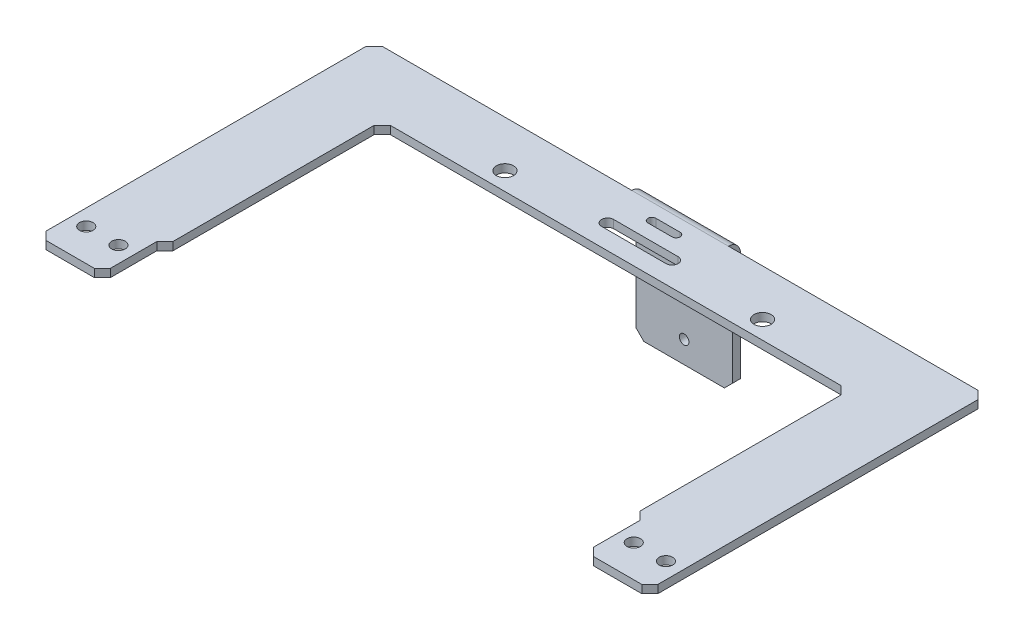
SolidWorks part; units mm, degrees
note: The reader was unsure of these and kept them because the rebuilt part matched: flange length of "Edge-Flange1".
material "5052-H32"
ref_plane "Front" through (0, 0, 0) normal (0, 0, 1) x (1, 0, 0)
ref_plane "Top" through (0, 0, 0) normal (0, 1, 0) x (1, 0, 0)
ref_plane "Right" through (0, 0, 0) normal (1, 0, 0) x (0, 0, -1)
sketch "Sketch1" plane through (0, 0, 0) normal (0, 1, 0) x (1, 0, 0)
  line L0 (0, 0) -> (331.8997, 0) construction
  line L1 (0, 12.7) -> (337.5621, 12.7) construction
  line L2 (0, 24.638) -> (331.8997, 24.638) construction
  line L7 (25.4, 0) -> (0, 0)
  line L8 (0, 0) -> (0, 132.588)
  line L11 (25.4, 0) -> (25.4, 21.463)
  line L12 (25.4, 21.463) -> (28.575, 24.638)
  line L13 (28.575, 24.638) -> (28.575, 107.188)
  line L14 (120.65, 24.638) -> (120.65, 107.188) construction
  line L15 (212.725, 24.638) -> (212.725, 107.188)
  line L16 (215.9, 21.463) -> (212.725, 24.638)
  line L17 (215.9, 0) -> (215.9, 21.463)
  line L18 (241.3, 0) -> (241.3, 132.588)
  line L19 (215.9, 0) -> (241.3, 0)
  line L20 (28.575, 107.188) -> (212.725, 107.188)
  line L21 (0, 132.588) -> (241.3, 132.588)
  line L22 (167.7838, 107.95) -> (164.1177, 114.3) construction
  line L23 (77.1823, 114.3) -> (73.5162, 120.65) construction
  line L24 (73.5162, 120.65) -> (66.1838, 120.65) construction
  line L25 (66.1838, 120.65) -> (62.5177, 114.3) construction
  line L26 (62.5177, 114.3) -> (66.1838, 107.95) construction
  line L27 (66.1838, 107.95) -> (73.5162, 107.95) construction
  line L28 (73.5162, 107.95) -> (77.1823, 114.3) construction
  line L29 (175.1162, 107.95) -> (167.7838, 107.95) construction
  line L30 (178.7823, 114.3) -> (175.1162, 107.95) construction
  line L31 (175.1162, 120.65) -> (178.7823, 114.3) construction
  line L32 (167.7838, 120.65) -> (175.1162, 120.65) construction
  line L33 (164.1177, 114.3) -> (167.7838, 120.65) construction
  circle A0 centre (6.35, 12.7) radius 2.667
  circle A1 centre (19.05, 12.7) radius 2.667
  circle A2 centre (222.25, 12.7) radius 2.667
  circle A3 centre (234.95, 12.7) radius 2.667
  circle A4 centre (69.85, 114.3) radius 6.35 construction
  circle A5 centre (69.85, 114.3) radius 3.3782
  circle A6 centre (171.45, 114.3) radius 6.35 construction
  circle A7 centre (171.45, 114.3) radius 3.3782
  dimension "D2" = 5.334
  dimension "D12" = 6.7564
  dimension "D1" = 11.938
  dimension "D3" = 12.7
  dimension "D4" = 6.35
  dimension "D5" = 12.7
  dimension "D6" = 3.175
  dimension "D7" = 45
  dimension "D8" = 25.4
  dimension "D9" = 92.075
  dimension "D10" = 82.55
  dimension "D11" = 25.4
  dimension "D13" = 101.6
  dimension "D14" = 50.8
  dimension "D15" = 12.7
base flange "Base-Flange1" sketch "Sketch1" thickness 3.175 reverse thickness direction yes parameters "D1"=1.5875
chamfer "Chamfer2" distance 3.175 angle 45 8 edges at (241.3, 1.5875, -132.588) (241.3, 1.5875, 0) (215.9, 1.5875, 0) (212.725, 1.5875, -107.188) (28.575, 1.5875, -107.188) (25.4, 1.5875, 0) (0, 1.5875, 0) (0, 1.5875, -132.588)
edge flange "Edge-Flange1" sketch "Sketch8" flange angle 90 flange length 50.8 flange position bend outside bend radius 1.5875 thickness 3.175 relief rectangular parameters "D6"=10
sketch "Sketch8" plane through (0, 0, -132.588) normal (0, 0, -1) x (1, 0, 0)
  line L1 (139.7, 0) -> (101.6, 0)
  line L2 (101.6, 0) -> (101.6, 47.625)
  line L3 (101.6, 47.625) -> (139.7, 47.625)
  line L4 (139.7, 47.625) -> (139.7, 0)
  line L6 (238.125, 0) -> (3.175, 0) construction
  line L7 (120.65, -3.175) -> (120.65, 0) construction
  line L8 (238.125, -3.175) -> (3.175, -3.175) construction
  line L9 (120.65, 0) -> (120.65, 47.625) construction
  dimension "D1" = 38.1
bend "EdgeBend1" bend radius 1.5875 bend angle 90 parameters "D5"=1
chamfer "Chamfer3" distance 3.175 angle 45 2 edges at (139.7, -47.625, -135.763) (101.6, -47.625, -135.763)
sketch "Sketch9" plane through (0, 0, -137.3505) normal (0, 0, -1) x (-1, 0, 0)
  line L0 (-120.65, -47.625) -> (-120.65, -38.989) construction
  line L1 (-136.525, -47.625) -> (-104.775, -47.625) construction
  line L2 (-120.65, -38.989) -> (-120.65, -19.939) construction
  circle A0 centre (-120.65, -38.989) radius 1.905
  circle A1 centre (-120.65, -19.939) radius 1.905
  dimension "D1" = 3.81
  dimension "D3" = 8.636
  dimension "D2" = 19.05
extrude "Cut-Extrude1" cut sketch "Sketch9" against normal through all normal cut yes
sketch "Sketch10" plane through (0, 3.175, 0) normal (0, 1, 0) x (1, 0, 0)
  line L0 (120.65, 132.588) -> (120.65, 107.188) construction
  line L1 (139.7, 132.588) -> (101.6, 132.588) construction
  line L2 (31.75, 107.188) -> (209.55, 107.188) construction
  line L3 (115.8875, 126.238) -> (125.4125, 126.238) construction
  line L4 (115.8875, 127.8255) -> (125.4125, 127.8255)
  line L5 (115.8875, 124.6505) -> (125.4125, 124.6505)
  line L6 (238.125, 132.588) -> (139.7, 132.588) construction
  arc A0 (115.8875, 127.8255) -> (115.8875, 124.6505) centre (115.8875, 126.238) ccw
  arc A1 (125.4125, 124.6505) -> (125.4125, 127.8255) centre (125.4125, 126.238) ccw
  point P8 (120.65, 126.238)
  dimension "D2" = 3.175
  dimension "D1" = 9.525
  dimension "D3" = 6.35
extrude "Cut-Extrude2" cut sketch "Sketch10" against normal through all normal cut yes
sketch "Sketch11" plane through (0, 3.175, 0) normal (0, 1, 0) x (1, 0, 0)
  line L0 (120.65, 107.188) -> (120.65, 132.588) construction
  line L1 (31.75, 107.188) -> (209.55, 107.188) construction
  line L2 (139.7, 132.588) -> (101.6, 132.588) construction
  line L3 (107.95, 116.713) -> (133.35, 116.713) construction
  line L4 (107.95, 119.0943) -> (133.35, 119.0943)
  line L5 (107.95, 114.3318) -> (133.35, 114.3318)
  arc A0 (107.95, 119.0943) -> (107.95, 114.3318) centre (107.95, 116.713) ccw
  arc A1 (133.35, 114.3318) -> (133.35, 119.0943) centre (133.35, 116.713) ccw
  point P8 (120.65, 116.713)
  dimension "D1" = 9.525
  dimension "D2" = 4.7625
  dimension "D3" = 25.4
extrude "Cut-Extrude3" cut sketch "Sketch11" against normal through all normal cut yes
sketch "Bend-Lines1" [suppressed] plane through (0, 0, 0) normal (0, 1, 0) x (1, 0, 0)
sketch "Bounding-Box1" [suppressed] plane through (0, 0, 0) normal (0, 1, 0) x (1, 0, 0)
sheet metal parameters "Sheet-Metal2" thickness 3.175 parameters "D1"=1.5875
flat pattern "Flat-Pattern2" [suppressed]
sketch "Bend-Lines2" plane through (0, 0, 0) normal (0, 1, 0) x (1, 0, 0)
sketch3d "Bounding-Box2" [suppressed]
  line L0 (-241.3, 129.413, 0) -> (0, 129.413, 0) construction
  line L1 (-241.3, 0, 0) -> (0, 0, 0) construction
  line L2 (-241.3, 129.413, 0) -> (-241.3, 0, 0) construction
  line L3 (0, 129.413, 0) -> (0, 0, 0) construction
sheet metal parameters "Sheet-Metal3" thickness 3.175 parameters "D1"=1.5875
flat pattern "Flat-Pattern2"
sketch "Bend-Lines2" plane through (0, 0, 0) normal (0, -1, 0) x (-1, 0, 0)
  line L0 (-107.95, 131.9066) -> (-133.35, 131.9066) construction
  line L1 (-107.95, 131.9066) -> (-133.35, 131.9066) construction
sketch3d "Bounding-Box2" [suppressed]
  line L0 (-241.3, 193.1378, 0) -> (0, 193.1378, 0) construction
  line L1 (-241.3, 0, 0) -> (0, 0, 0) construction
  line L2 (-241.3, 193.1378, 0) -> (-241.3, 0, 0) construction
  line L3 (0, 193.1378, 0) -> (0, 0, 0) construction
bend of the flat pattern "Flatten-<EdgeBend1>1"
sheet metal parameters "Sheet-Metal4" thickness 3.175 parameters "D1"=1.5875
flat pattern "Flat-Pattern2"
sketch "Bend-Lines2" plane through (0, 0, 0) normal (0, -1, 0) x (-1, 0, 0)
  line L0 (-107.95, 131.9066) -> (-133.35, 131.9066) construction
  line L1 (-107.95, 131.9066) -> (-133.35, 131.9066) construction
sketch3d "Bounding-Box2" [suppressed]
  line L0 (-241.3, 180.4378, 0) -> (0, 180.4378, 0) construction
  line L1 (-241.3, 0, 0) -> (0, 0, 0) construction
  line L2 (-241.3, 180.4378, 0) -> (-241.3, 0, 0) construction
  line L3 (0, 180.4378, 0) -> (0, 0, 0) construction
bend of the flat pattern "Flatten-<EdgeBend1>1"
sheet metal parameters "Sheet-Metal5" thickness 3.175 parameters "D1"=1.5875
flat pattern "Flat-Pattern2"
sketch "Bend-Lines2" plane through (0, 0, 0) normal (0, -1, 0) x (-1, 0, 0)
  line L0 (-101.6, 131.9066) -> (-139.7, 131.9066) construction
  line L1 (-101.6, 131.9066) -> (-139.7, 131.9066) construction
sketch3d "Bounding-Box2" [suppressed]
  line L0 (-241.3, 180.4378, 0) -> (0, 180.4378, 0) construction
  line L1 (-241.3, 0, 0) -> (0, 0, 0) construction
  line L2 (-241.3, 180.4378, 0) -> (-241.3, 0, 0) construction
  line L3 (0, 180.4378, 0) -> (0, 0, 0) construction
bend of the flat pattern "Flatten-<EdgeBend1>1"
sheet metal parameters "Sheet-Metal6" thickness 3.175 parameters "D1"=1.5875
flat pattern "Flat-Pattern2"
sketch "Bend-Lines2" plane through (0, 0, 0) normal (0, -1, 0) x (-1, 0, 0)
  line L0 (-101.6, 135.0816) -> (-139.7, 135.0816) construction
  line L1 (-101.6, 135.0816) -> (-139.7, 135.0816) construction
sketch3d "Bounding-Box2" [suppressed]
  line L0 (-241.3, 183.6128, 0) -> (0, 183.6128, 0) construction
  line L1 (-241.3, 0, 0) -> (0, 0, 0) construction
  line L2 (-241.3, 183.6128, 0) -> (-241.3, 0, 0) construction
  line L3 (0, 183.6128, 0) -> (0, 0, 0) construction
bend of the flat pattern "Flatten-<EdgeBend1>1"
